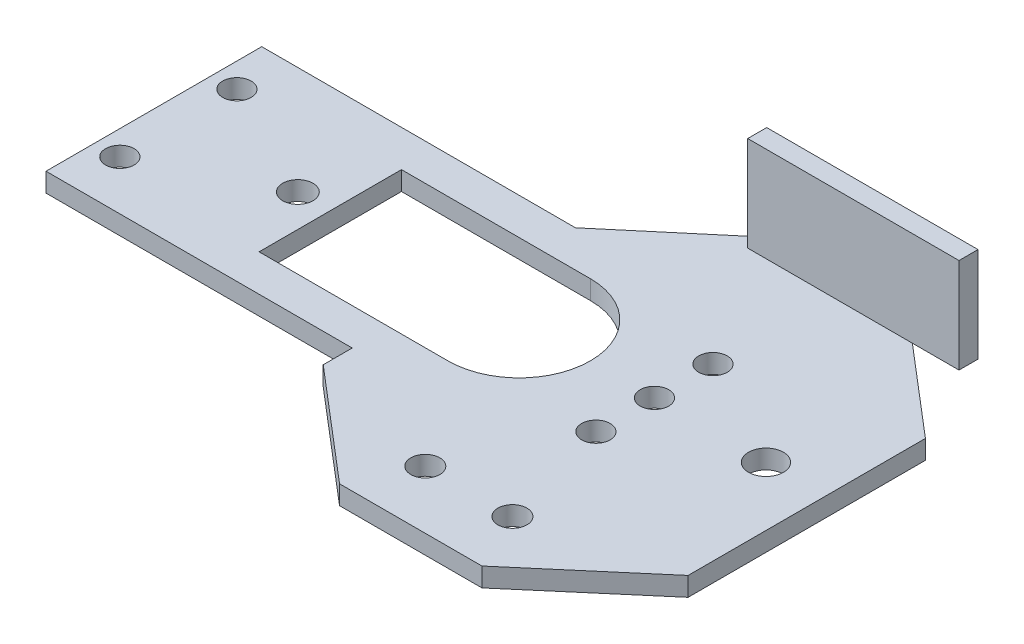
SolidWorks part; units mm, degrees
ref_plane "Alzado" through (0, 0, 0) normal (0, 0, 1) x (1, 0, 0)
ref_plane "Planta" through (0, 0, 0) normal (0, 1, 0) x (1, 0, 0)
ref_plane "Vista lateral" through (0, 0, 0) normal (1, 0, 0) x (0, 0, -1)
sketch "Croquis1" plane through (0, 0, 0) normal (0, 1, 0) x (1, 0, 0)
  line L0 (-26.5149, -10.5826) -> (-26.5149, -7.5272)
  line L1 (-14.7949, 24.4174) -> (0.2051, 24.4174)
  line L2 (-26.5149, -10.5826) -> (-14.7949, -20.5826)
  line L3 (-14.7949, -20.5826) -> (0.2051, -20.5826)
  line L4 (11.9251, 14.4174) -> (11.9251, -10.5826)
  line L5 (-7.2949, -20.5826) -> (-7.2949, 24.4174) construction
  line L6 (-26.5149, -7.5272) -> (-40.887, -7.5272)
  line L7 (11.9251, -10.5826) -> (0.2051, -20.5826)
  line L8 (-25.725, 15.2001) -> (-14.7949, 24.4174)
  line L9 (0.2051, 24.4174) -> (11.9251, 14.4174)
  line L10 (-14.7949, -20.5826) -> (-14.7949, 24.4174) construction
  line L11 (0.2051, -20.5826) -> (0.2051, 24.4174) construction
  line L12 (-14.7949, -2.3239) -> (0.2051, -2.3239) construction
  line L13 (11.9251, -10.5826) -> (-26.5149, -10.5826) construction
  line L14 (11.9251, 14.4174) -> (-27.2565, 14.4174) construction
  line L15 (-41.4058, 15.2001) -> (-25.725, 15.2001)
  line L16 (-11.8849, -14.4576) -> (-2.7049, -14.4576) construction
  line L17 (-20.2949, 3.8424) -> (5.7051, 3.8424) construction
  line L18 (-52.2565, 3.8424) -> (-52.2565, 28.8425) construction
  line L19 (-40.1956, 11.3424) -> (-20.2949, 11.3424)
  line L20 (-40.1956, 11.3424) -> (-40.1956, -3.6576)
  line L21 (-40.1956, -3.6576) -> (-20.2949, -3.6576)
  line L22 (-20.2949, 3.8424) -> (-52.2565, 3.8424) construction
  line L23 (-27.2565, 14.4174) -> (-27.2565, 26.4393) construction
  line L24 (-41.4058, 15.2001) -> (-58.7725, 15.2001)
  line L25 (-58.7725, 15.2001) -> (-58.7725, -7.5272)
  line L26 (-58.7725, -7.5272) -> (-40.887, -7.5272)
  line L27 (-6.0449, 10.0086) -> (-6.0449, -2.3239) construction
  line L28 (-14.7949, 10.0086) -> (0.2051, 10.0086) construction
  line L29 (-14.7949, 10.0086) -> (-58.7725, 10.0086) construction
  line L30 (-14.7949, -2.3239) -> (-58.7725, -2.3239) construction
  line L31 (-56.1949, 15.2001) -> (-56.1949, -7.5272) construction
  line L32 (-25.725, 15.2001) -> (-25.725, 14.4174) construction
  arc A0 (-41.4058, 15.2001) -> (-40.887, -7.5272) centre (-40.887, 3.8424) ccw construction
  circle A1 centre (-11.8849, -14.4576) radius 1.53
  circle A2 centre (-2.7049, -14.4576) radius 1.53
  arc A3 (-20.2949, -3.6576) -> (-20.2949, 11.3424) centre (-20.2949, 3.8424) ccw
  circle A4 centre (5.7051, 3.8424) radius 1.8379
  circle A5 centre (-43.6105, 3.8424) radius 1.5973
  circle A6 centre (-6.0449, 3.8424) radius 1.5
  circle A7 centre (-6.0449, 10.0086) radius 1.5
  circle A8 centre (-6.0449, -2.3239) radius 1.5
  circle A9 centre (-20.2949, 3.8424) radius 7.5 construction
  circle A10 centre (-56.1949, 10.0086) radius 1.5
  circle A11 centre (-56.1949, -2.3239) radius 1.5
  point P0 (0, 0)
  point P16 (0, 0)
  dimension "D12" = 3
  dimension "D13" = 15
  dimension "D10" = 3.06
  dimension "D1" = 15
  dimension "D2" = 10
  dimension "D3" = 45
  dimension "D4" = 10
  dimension "D5" = 6.125
  dimension "D6" = 26
  dimension "D7" = 18.3
  dimension "D8" = 9.18
  dimension "D9" = 25
  dimension "D11" = 14.25
  dimension "D14" = 48.9
extrude "Saliente-Extruir1" add sketch "Croquis1" along normal blind 2
sketch "Croquis2" plane through (0, 2, 0) normal (0, 1, 0) x (1, 0, 0)
  line L1 (-14.7949, 24.4174) -> (7.4645, 24.4174)
  line L2 (-14.7949, 24.4174) -> (-14.7949, 22.4174)
  line L3 (-14.7949, 22.4174) -> (7.4645, 22.4174)
  line L4 (7.4645, 24.4174) -> (7.4645, 22.4174)
  dimension "D1" = 2
extrude "Saliente-Extruir2" add sketch "Croquis2" along normal blind 10
sketch "Croquis3" plane through (0, 0, 0) normal (0, -1, 0) x (1, 0, 0)
  line L1 (0.2051, -24.4174) -> (-7.3584, -24.4174)
  line L2 (0.2051, -24.4174) -> (0.2051, -22.4174)
  line L3 (0.2051, -22.4174) -> (-7.3584, -22.4174)
  line L4 (-7.3584, -24.4174) -> (-7.3584, -22.4174)
  dimension "D1" = 2
extrude "Saliente-Extruir3" add sketch "Croquis3" along normal blind 10
